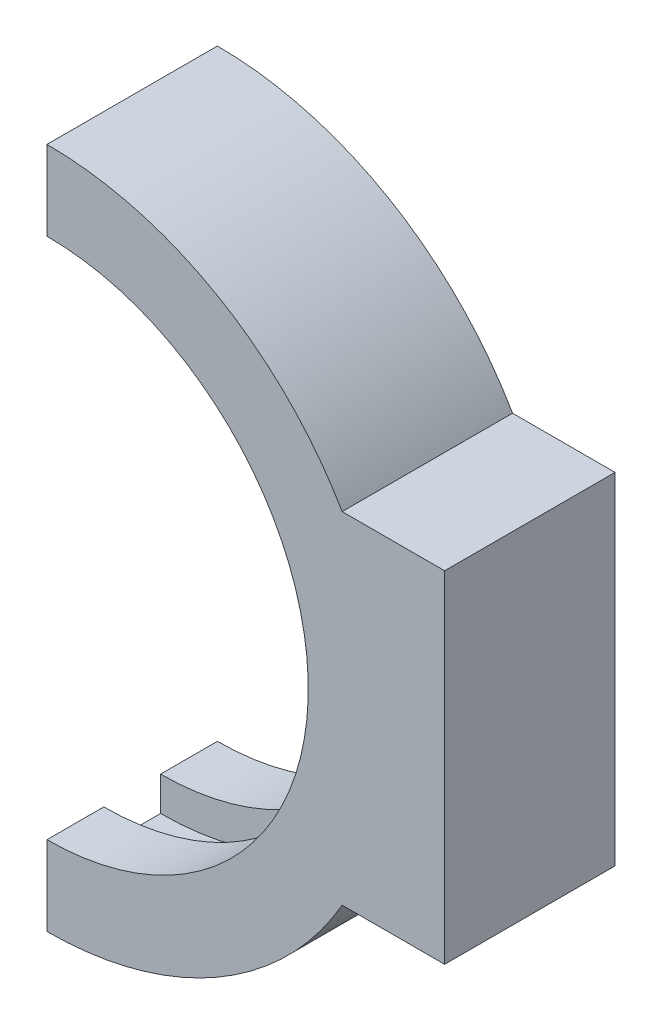
SolidWorks part; units mm, degrees
ref_plane "Front Plane" through (0, 0, 0) normal (0, 0, 1) x (1, 0, 0)
ref_plane "Top Plane" through (0, 0, 0) normal (0, 1, 0) x (1, 0, 0)
ref_plane "Right Plane" through (0, 0, 0) normal (1, 0, 0) x (0, 0, -1)
sketch "Sketch1" plane through (0, 0, 0) normal (0, 0, 1) x (1, 0, 0)
  line L0 (0, 26.4851) -> (0, 30.4851)
  line L1 (0, -25.5149) -> (0, -29.5149)
  line L2 (30, 15.4851) -> (30, -14.5149) construction
  line L3 (25.9808, 15.4851) -> (35, 15.4851)
  line L4 (25.9808, -14.5149) -> (35, -14.5149)
  line L5 (0, 0.4851) -> (66.6758, 0.4851) construction
  line L6 (35, 15.4851) -> (35, -14.5149) construction
  line L7 (35, -14.5149) -> (35, 15.4851)
  arc A0 (0, 26.4851) -> (0, -25.5149) centre (0, 0.4851) cw
  arc A1 (0, 30.4851) -> (25.9808, 15.4851) centre (0, 0.4851) cw
  arc A2 (25.9808, -14.5149) -> (0, -29.5149) centre (0, 0.4851) cw
  point P10 (26, 0.4851)
  dimension "D1" = 26
  dimension "D6" = 4
  dimension "D2" = 4
  dimension "D3" = 4
  dimension "D4" = 30
  dimension "D5" = 5
extrude "Boss-Extrude1" add sketch "Sketch1" along normal blind 5
ref_plane "Plane1" through (0, 0, 5) normal (0, 0, 1) x (1, 0, 0)
sketch "Sketch2" plane through (0, 0, 5) normal (0, 0, 1) x (1, 0, 0)
  line L0 (0, 26.4851) -> (0, 23.4851)
  line L1 (0, -25.5149) -> (0, -22.5149)
  line L2 (0, 26.4851) -> (0, 30.4851)
  line L3 (0, -25.5149) -> (0, -29.5149) construction
  line L4 (0, -25.5149) -> (0, -29.5149)
  line L5 (25.9808, 15.4851) -> (35, 15.4851)
  line L6 (35, 15.4851) -> (35, -14.5149)
  line L7 (35, -14.5149) -> (25.9808, -14.5149)
  arc A0 (0, 23.4851) -> (0, -22.5149) centre (0, 0.4851) cw
  arc A1 (0, 30.4851) -> (25.9808, 15.4851) centre (0, 0.4851) cw
  arc A2 (0, -29.5149) -> (25.9808, -14.5149) centre (0, 0.4851) ccw construction
  arc A3 (25.9808, -14.5149) -> (0, -29.5149) centre (0, 0.4851) cw
  dimension "D1" = 3
  dimension "D2" = 3
extrude "Boss-Extrude2" add sketch "Sketch2" along normal blind 5
ref_plane "Plane2" through (0, 0, 0) normal (0, 0, -1) x (-1, 0, 0)
sketch "Sketch3" plane through (0, 0, 0) normal (0, 0, -1) x (-1, 0, 0)
  line L2 (0, -22.5149) -> (0, -29.5149)
  line L10 (0, 30.4851) -> (0, 23.4851)
  line L11 (-25.9808, 15.4851) -> (-35, 15.4851)
  line L12 (-35, 15.4851) -> (-35, -14.5149)
  line L13 (-35, -14.5149) -> (-25.9808, -14.5149)
  arc A1 (-25.9808, -14.5149) -> (0, -29.5149) centre (0, 0.4851) ccw
  arc A4 (0, 23.4851) -> (0, -22.5149) centre (0, 0.4851) ccw construction
  arc A6 (0, 23.4851) -> (0, -22.5149) centre (0, 0.4851) ccw
  arc A7 (0, 30.4851) -> (-25.9808, 15.4851) centre (0, 0.4851) ccw
extrude "Boss-Extrude4" add sketch "Sketch3" along normal blind 5
